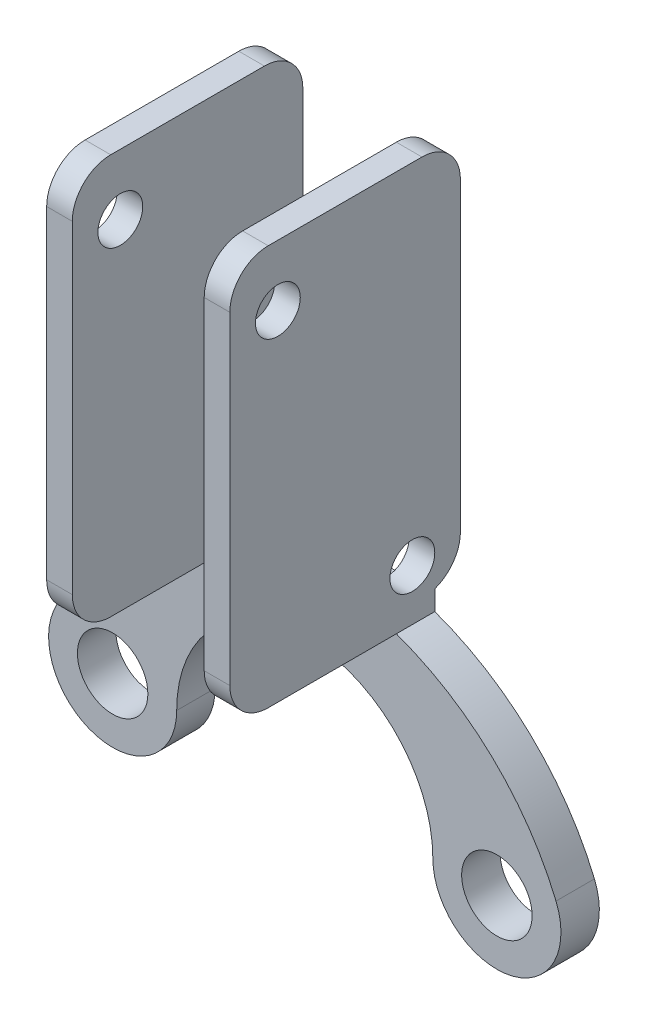
SolidWorks part; units mm, degrees
ref_plane "Front Plane" through (0, 0, 0) normal (0, 0, 1) x (1, 0, 0)
ref_plane "Top Plane" through (0, 0, 0) normal (0, 1, 0) x (1, 0, 0)
ref_plane "Right Plane" through (0, 0, 0) normal (1, 0, 0) x (0, 0, -1)
sketch "Sketch2" plane through (0, 0, 0) normal (0, 0, 1) x (1, 0, 0)
  line L0 (0, 60) -> (-5.15, 60)
  line L1 (-30, 60) -> (30, 60) construction
  line L2 (0, 60) -> (5.15, 60)
  line L3 (-5.15, 60) -> (-5.15, 55)
  line L4 (-5.15, 60) -> (5.15, 60)
  line L5 (-5.15, 60) -> (-5.15, 90)
  line L6 (-5.15, 90) -> (5.15, 90)
  line L7 (5.15, 60) -> (5.15, 90)
  line L8 (-5.15, 55) -> (5.15, 55)
  line L9 (5.15, 55) -> (5.15, 60)
  line L10 (5.15, 90) -> (7.15, 90)
  line L11 (-5.15, 90) -> (-7.15, 90)
  line L12 (-7.15, 90) -> (-7.15, 55)
  line L13 (-7.15, 55) -> (-5.15, 55)
  line L14 (5.15, 55) -> (7.15, 55)
  line L15 (7.15, 55) -> (7.15, 90)
  circle A0 centre (15, 45) radius 2.75
  circle A1 centre (-15, 45) radius 2.75
  circle A2 centre (-15, 45) radius 5
  circle A3 centre (15, 45) radius 5
  arc A4 (10, 45) -> (-10, 45) centre (0, 45) ccw
  arc A5 (19.6154, 46.9231) -> (-19.6154, 46.9231) centre (0, 38.75) ccw
  circle M12 centre (15, 45) radius 2.75
  circle M13 centre (-15, 45) radius 2.75
  line M19 (30, 60) -> (-30, 60)
  dimension "D1" = 10
  dimension "D2" = 10
  dimension "D3" = 5.15
  dimension "D4" = 5.15
  dimension "D5" = 30
  dimension "D6" = 5
  dimension "D7" = 2
  dimension "D8" = 2
extrude "Boss-Extrude1" add sketch "Sketch2" along normal blind 3 contours L12 A5 A2 A4 L8 L13 | A2 M13 | A3 A5 L15 L14 L8 A4 | A3 M12 | L9 A5 L3 L8 | L15 A5 L9 L14 | L3 A5 L12 L13 | L11 L12 L5 M19 | A5 L3 L12 M19 | A5 L3 M19 | A5 L9 M19 | A5 L15 L9 M19 | L15 L10 L7 M19 region at (-3.8664, 59.8104, 0) region at (3.8664, 59.8104, 0) region at (0, 57.3988, 0) region at (-6.15, 75, 0) region at (-6.2598, 59.5242, 0) region at (6.2598, 59.5242, 0) region at (6.15, 75, 0) region at (6.1253, 57.0446, 0) region at (-6.1253, 57.0446, 0) region at (10.8245, 52.8564, 0) region at (-10.8245, 52.8564, 0) region at (19.7642, 45.9528, 0) region at (-14.0472, 49.7642, 0)
sketch "Sketch3" plane through (0, 0, 3) normal (0, 0, 1) x (1, 0, 0)
  line L1 (-7.15, 58.761) -> (-5.15, 58.761)
  line L2 (-7.15, 58.761) -> (-7.15, 90)
  line L3 (-7.15, 90) -> (-5.15, 90)
  line L4 (-5.15, 58.761) -> (-5.15, 90)
  line L5 (7.15, 58.761) -> (5.15, 58.761)
  line L6 (7.15, 58.761) -> (7.15, 90)
  line L7 (7.15, 90) -> (5.15, 90)
  line L8 (5.15, 58.761) -> (5.15, 90)
extrude "Boss-Extrude2" add sketch "Sketch3" along normal blind 13
sketch "Sketch4" plane through (0, 0, 0) normal (0, 0, -1) x (-1, 0, 0)
  line L1 (-7.15, 90) -> (-5.15, 90)
  line L2 (-7.15, 90) -> (-7.15, 60.3)
  line L3 (-7.15, 60.3) -> (-5.15, 60.3)
  line L4 (-5.15, 90) -> (-5.15, 60.3)
  line L5 (5.15, 60.3) -> (7.15, 60.3)
  line L6 (5.15, 60.3) -> (5.15, 90)
  line L7 (5.15, 90) -> (7.15, 90)
  line L8 (7.15, 60.3) -> (7.15, 90)
  dimension "D1" = 29.7
  dimension "D2" = 29.7
extrude "Boss-Extrude3" add sketch "Sketch4" along normal blind 2
sketch "Sketch5" plane through (7.15, 0, 0) normal (1, 0, 0) x (0, 0, -1)
  circle A0 centre (-1.75, 62.75) radius 1.75
  circle A1 centre (-12.25, 85.25) radius 1.75
  dimension "D1" = 3.5
  dimension "D2" = 3.5
extrude "Cut-Extrude1" cut sketch "Sketch5" against normal through all
fillet "Fillet1" radius 3 8 edges at (-6.15, 60.3, -2) (6.15, 60.3, -2) (6.15, 58.761, 16) (-6.15, 58.761, 16) (6.15, 90, -2) (-6.15, 90, -2) (6.15, 90, 16) (-6.15, 90, 16)
